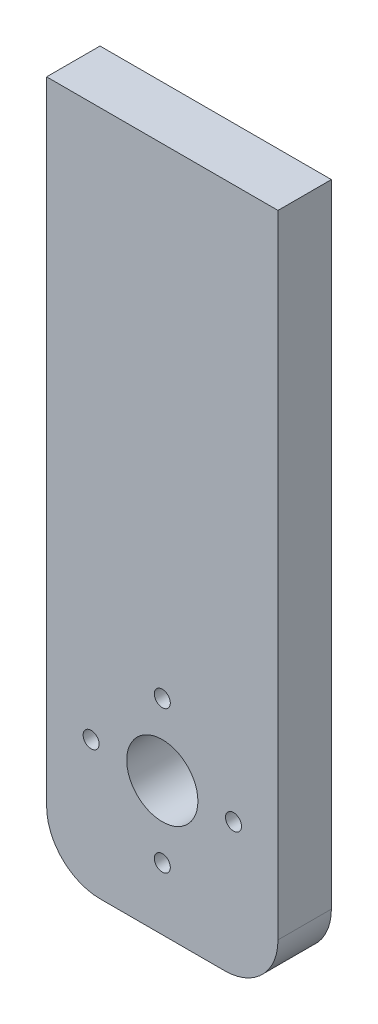
SolidWorks part; units mm, degrees
ref_plane "Plan de face" through (0, 0, 0) normal (0, 0, 1) x (1, 0, 0)
ref_plane "Plan de dessus" through (0, 0, 0) normal (0, 1, 0) x (1, 0, 0)
ref_plane "Plan de droite" through (0, 0, 0) normal (1, 0, 0) x (0, 0, -1)
sketch "Esquisse1" plane through (0, 0, 0) normal (0, 0, 1) x (1, 0, 0)
  line L0 (24.9164, -77.5735) -> (24.9164, -6.5735)
  line L1 (50.9164, -6.5735) -> (24.9164, -6.5735)
  line L2 (37.9164, 189.4329) -> (37.9164, -108.4772) construction
  line L3 (30.9164, -83.5735) -> (44.9164, -83.5735)
  line L11 (50.9164, -77.5735) -> (50.9164, -6.5735)
  arc A0 (44.9164, -83.5735) -> (50.9164, -77.5735) centre (44.9164, -77.5735) ccw
  arc A1 (24.9164, -77.5735) -> (30.9164, -83.5735) centre (30.9164, -77.5735) ccw
  circle A2 centre (29.9164, -68.5735) radius 0.9
  circle A3 centre (37.9164, -60.5735) radius 0.9
  circle A4 centre (45.9164, -68.5735) radius 0.9
  circle A5 centre (37.9164, -76.5735) radius 0.9
  circle A7 centre (37.9164, -68.5735) radius 4
  point P6 (50.9164, -83.5735)
  dimension "D3" = 6
  dimension "D6" = 1.8
  dimension "D7" = 1.8
  dimension "D8" = 1.8
  dimension "D9" = 1.8
  dimension "D4" = 8
  dimension "D1" = 77
  dimension "D5" = 15
extrude "Boss.-Extru.1" add sketch "Esquisse1" along normal blind 6
